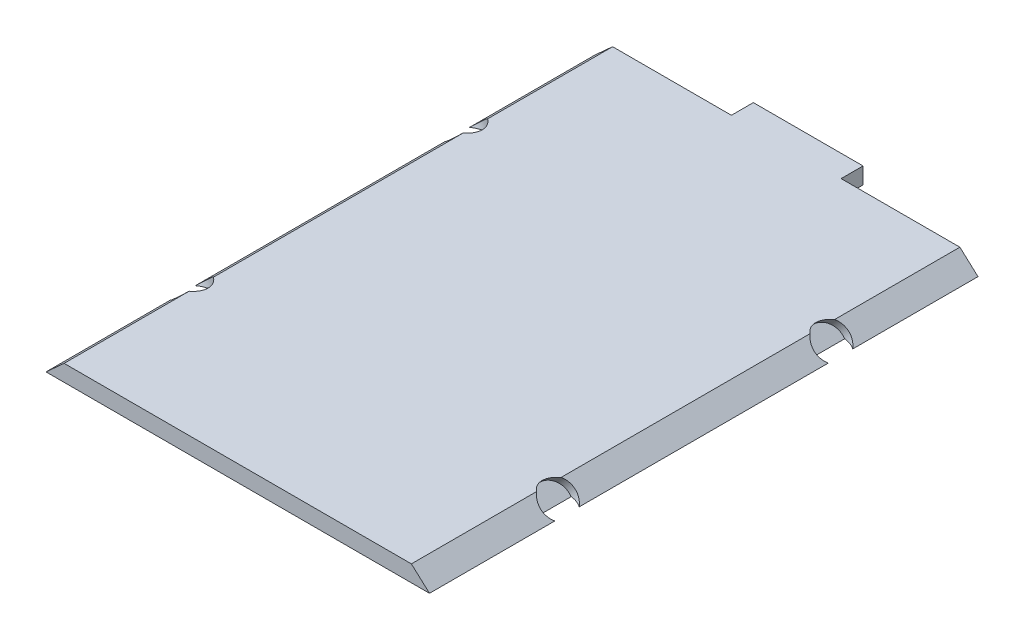
SolidWorks part; units mm, degrees
ref_plane "Front Plane" through (0, 0, 0) normal (0, 0, 1) x (1, 0, 0)
ref_plane "Top Plane" through (0, 0, 0) normal (0, 1, 0) x (1, 0, 0)
ref_plane "Right Plane" through (0, 0, 0) normal (1, 0, 0) x (0, 0, -1)
sketch "Sketch1" plane through (0, 0, 0) normal (0, 0, 1) x (1, 0, 0)
  line L0 (0, 0) -> (0, 44.45) construction
  line L1 (-40.2039, 5.9378) -> (40.2039, 5.9378)
  line L2 (-44.399, 2.1278) -> (44.399, 2.1278)
  line L3 (-40.2039, 5.9378) -> (-44.399, 2.1278)
  line L4 (40.2039, 5.9378) -> (44.399, 2.1278)
  arc A0 (44.399, 2.1278) -> (-44.399, 2.1278) centre (0, 0) ccw construction
  arc A1 (40.2039, 5.9378) -> (-40.2039, 5.9378) centre (0, 0) ccw construction
  dimension "D1" = 88.9
  dimension "D2" = 3.81
  dimension "D3" = 3.81
extrude "Boss-Extrude1" add sketch "Sketch1" along normal blind 127
sketch "Sketch2" plane through (0, 2.1278, 0) normal (0, -1, 0) x (1, 0, 0)
  line L0 (-44.399, 0) -> (44.399, 0) construction
  line L1 (-12.7, 0) -> (12.7, 0)
  line L2 (-12.7, 0) -> (-12.7, -5.08)
  line L3 (-12.7, -5.08) -> (12.7, -5.08)
  line L4 (12.7, 0) -> (12.7, -5.08)
  line L5 (0, 0) -> (0, -5.08) construction
  line L6 (0, 0) -> (0, 127) construction
  line L7 (-44.399, 127) -> (44.399, 127) construction
  dimension "D1" = 25.4
  dimension "D2" = 5.08
  dimension "D3" = 0
extrude "Boss-Extrude2" add sketch "Sketch2" against normal blind 3.81
sketch "Sketch3" plane through (-21.1272, 23.263, 0) normal (-0.6723, 0.7403, 0) x (0.7403, 0.6723, 0)
  line L0 (-28.6033, 0) -> (-28.6033, -127.0183) construction
  line L1 (-25.7698, 0) -> (-31.4368, 0) construction
  line L2 (-25.7698, -63.5) -> (-31.4368, -63.5) construction
  line L3 (-25.7698, -127) -> (-25.7698, 0) construction
  line L4 (-31.4368, -127) -> (-31.4368, 0) construction
  circle A0 centre (-28.6033, -31.7592) radius 4
  circle A1 centre (-28.6033, -95.2408) radius 4
  point P12 (-28.6033, -63.5092)
  dimension "D1" = 8
  dimension "D2" = 31.75
extrude "Cut-Extrude1" cut sketch "Sketch3" against normal blind 2
sketch "Sketch4" plane through (21.1272, 23.263, 0) normal (0.6723, 0.7403, 0) x (0.7403, -0.6723, 0)
  line L0 (28.6033, -127) -> (28.6033, 0.1686) construction
  line L1 (31.4368, -127) -> (25.7698, -127) construction
  line L2 (25.7698, -63.5) -> (31.4368, -63.5) construction
  line L3 (25.7698, -127) -> (25.7698, 0) construction
  line L4 (31.4368, -127) -> (31.4368, 0) construction
  circle A0 centre (28.6033, -95.1657) radius 4
  circle A1 centre (28.6033, -31.8343) radius 4
  point P12 (0, 0)
  point P13 (28.6033, -63.4157)
  dimension "D1" = 8
  dimension "D2" = 31.75
extrude "Cut-Extrude2" cut sketch "Sketch4" against normal blind 2
